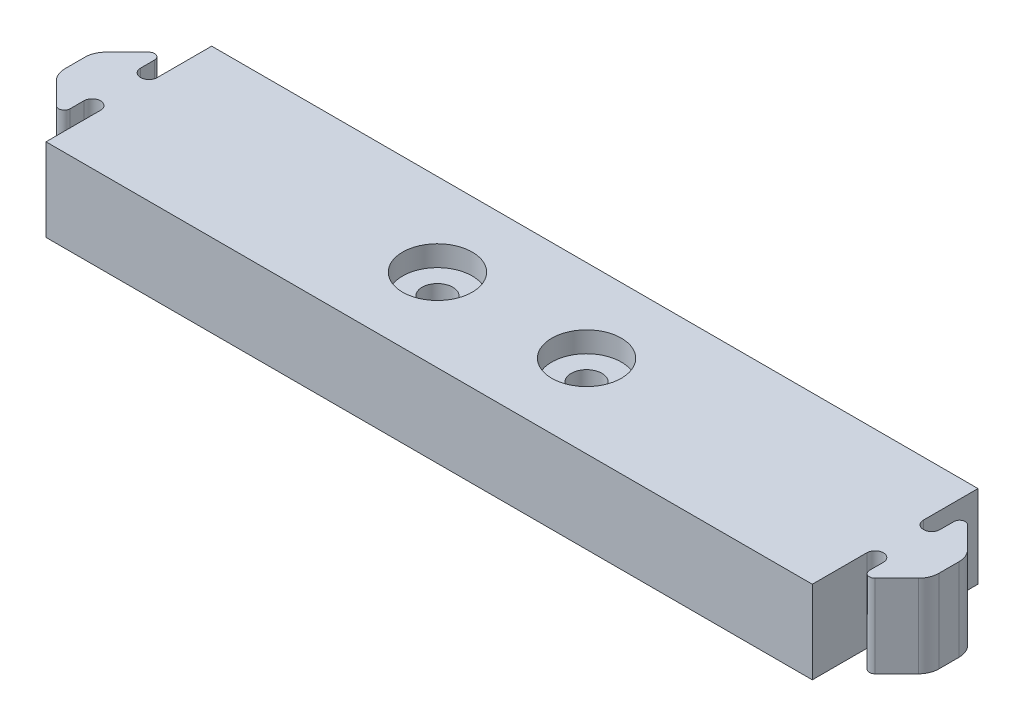
SolidWorks part; units mm, degrees
ref_plane "Front Plane" through (0, 0, 0) normal (0, 0, 1) x (1, 0, 0)
ref_plane "Top Plane" through (0, 0, 0) normal (0, 1, 0) x (1, 0, 0)
ref_plane "Right Plane" through (0, 0, 0) normal (1, 0, 0) x (0, 0, -1)
sketch "Sketch1" plane through (0, 0, 0) normal (0, 1, 0) x (1, 0, 0)
  line L0 (12.1572, -15.7678) -> (7.8138, -15.7678)
  line L1 (0, 0) -> (-117.475, 0)
  line L2 (0, 0) -> (0, -25.4)
  line L3 (0, -25.4) -> (-117.475, -25.4)
  line L4 (-117.475, 0) -> (-117.475, -25.4)
  line L13 (7.8138, -13.2278) -> (5.6802, -13.2278)
  line L14 (5.0695, -11.7535) -> (8.3922, -8.4308)
  line L15 (10.6437, -7.5166) -> (12.1572, -7.5166)
  line L16 (12.1572, -7.5166) -> (12.1572, -15.7678)
  arc A0 (7.8138, -15.7678) -> (7.8138, -13.2278) centre (7.8138, -14.4978) ccw
  arc A1 (5.6802, -13.2278) -> (5.0695, -11.7535) centre (5.6802, -12.3642) cw
  arc A2 (8.3922, -8.4308) -> (10.6437, -7.5166) centre (10.6216, -10.6915) cw
  point P18 (11.4004, -7.5166)
  dimension "D5" = 6.477
  dimension "D7" = 1.27
  dimension "D8" = 0.8636
  dimension "D9" = 3.175
  dimension "D1" = 117.475
  dimension "D2" = 25.4
  dimension "D3" = 4.3434
  dimension "D4" = 8.2512
  dimension "D6" = 45
  dimension "D10" = 2.54
  dimension "D11" = 3.4036
  dimension "D12" = 5.0763
  dimension "D13" = 1.5356
  dimension "D14" = 4.3434
  dimension "D15" = 4.0143
extrude "Boss-Extrude1" add sketch "Sketch1" along normal blind 12.7 contours L1 L4 L3 L2
sketch "Sketch3" plane through (0, 12.7, 0) normal (0, 1, 0) x (1, 0, 0)
  line L0 (0, 0) -> (-117.475, 0) construction
  line L1 (-114.3, 0) -> (-3.175, 0)
  line L2 (-114.3, 0) -> (-114.3, -25.4)
  line L3 (-114.3, -25.4) -> (-3.175, -25.4)
  line L4 (-3.175, 0) -> (-3.175, -25.4)
  line L5 (0, -25.4) -> (-117.475, -25.4) construction
  line L6 (0, -25.4) -> (-117.475, -25.4) construction
  line L7 (-58.7375, 0) -> (-58.7375, -25.4)
  circle A0 centre (-47.3075, -12.7) radius 2.3495
  circle A1 centre (-70.1675, -12.7) radius 2.3495
  point P8 (-58.7375, 0)
  point P11 (-58.7375, -25.4)
  point P18 (-58.7375, -12.7)
  dimension "D3" = 12.7
  dimension "D7" = 4.699
  dimension "D8" = 4.699
  dimension "D1" = 111.125
  dimension "D2" = 0
  dimension "D4" = 22.86
  dimension "D5" = 12.7
  dimension "D6" = 11.43
ref_plane "Plane1" through (-58.7375, 0, 0) normal (-1, 0, 0) x (0, 0, 1)
sketch "Sketch10" plane through (0, 12.7, 0) normal (0, 1, 0) x (1, 0, 0)
  line L5 (0, -12.7) -> (0, -8.3566)
  line L6 (2.54, -8.3566) -> (2.54, -6.223)
  line L7 (4.0143, -5.6123) -> (7.337, -8.935)
  line L8 (8.2512, -11.1865) -> (8.2512, -12.7)
  line L9 (8.2512, -12.7) -> (0, -12.7)
  line L10 (-58.7375, 8.382) -> (-58.7375, -8.382) construction
  line L11 (0, 0) -> (0, -25.4) construction
  line L12 (-117.475, -12.7) -> (-117.475, -8.3566)
  line L13 (-120.015, -8.3566) -> (-120.015, -6.223)
  line L14 (-121.4893, -5.6123) -> (-124.812, -8.935)
  line L15 (-125.7262, -11.1865) -> (-125.7262, -12.7)
  line L16 (-125.7262, -12.7) -> (-117.475, -12.7)
  arc A3 (0, -8.3566) -> (2.54, -8.3566) centre (1.27, -8.3566) ccw
  arc A4 (2.54, -6.223) -> (4.0143, -5.6123) centre (3.4036, -6.223) cw
  arc A5 (7.337, -8.935) -> (8.2512, -11.1865) centre (5.0763, -11.1644) cw
  arc A6 (-117.475, -8.3566) -> (-120.015, -8.3566) centre (-118.745, -8.3566) cw
  arc A7 (-120.015, -6.223) -> (-121.4893, -5.6123) centre (-120.8786, -6.223) ccw
  arc A8 (-124.812, -8.935) -> (-125.7262, -11.1865) centre (-122.5513, -11.1644) ccw
  point P2 (0, -12.7)
extrude "Boss-Extrude7" add sketch "Sketch10" against normal blind 12.7
mirror "Mirror1" about plane through (8.2512, 0, 12.7) normal (0, 0, 1) of "Boss-Extrude7"
extrude "Cut-Extrude1" cut sketch "Sketch3" against normal through all contours A1 | A0
sketch "Sketch11" plane through (0, 0, 0) normal (0, -1, 0) x (-1, 0, 0)
  circle A0 centre (70.1675, -12.7) radius 5.08
  circle A1 centre (47.3075, -12.7) radius 5.08
extrude "Cut-Extrude2" cut sketch "Sketch11" against normal blind 3.81
sketch "Sketch13" plane through (0, 12.7, 0) normal (0, 1, 0) x (1, 0, 0)
  circle A0 centre (-70.1675, -12.7) radius 5.334
sketch "Sketch14" plane through (0, 12.7, 0) normal (0, 1, 0) x (1, 0, 0)
  circle A0 centre (-47.3075, -12.7) radius 5.334
extrude "Cut-Extrude3" cut sketch "Sketch14" against normal blind 3.175
extrude "Cut-Extrude4" cut sketch "Sketch13" against normal blind 3.175 contours A0
